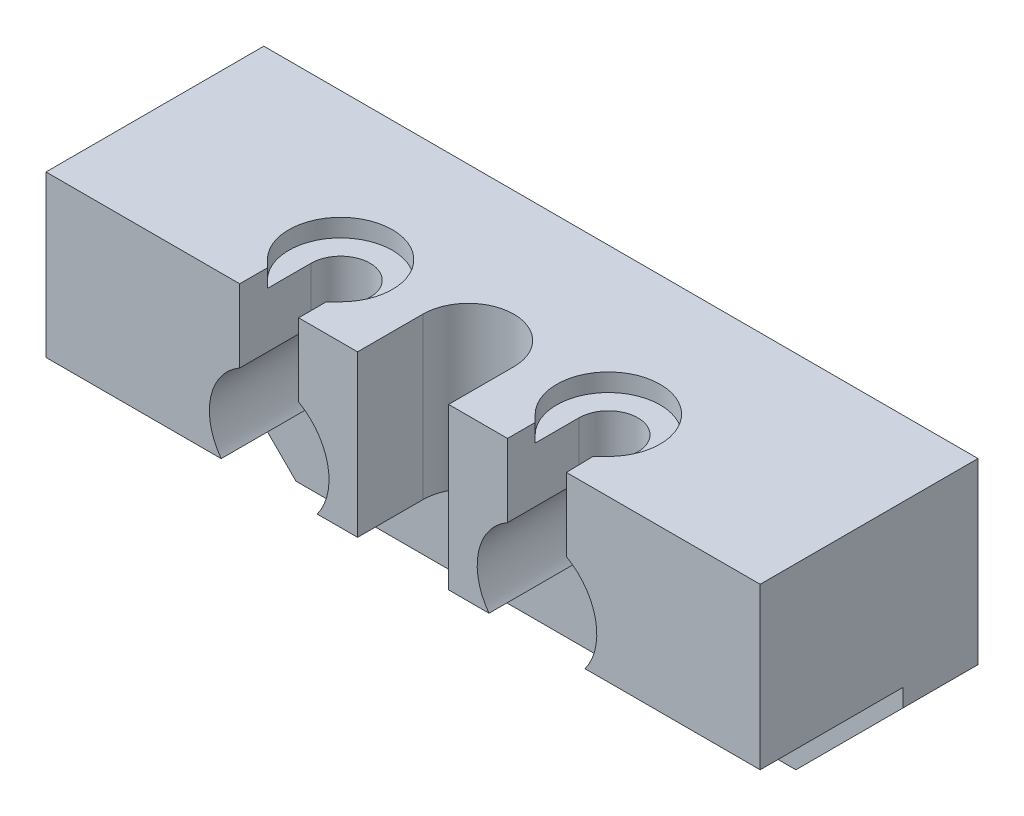
SolidWorks part; units mm, degrees
ref_plane "Front Plane" through (0, 0, 0) normal (0, 0, 1) x (1, 0, 0)
ref_plane "Top Plane" through (0, 0, 0) normal (0, 1, 0) x (1, 0, 0)
ref_plane "Right Plane" through (0, 0, 0) normal (1, 0, 0) x (0, 0, -1)
sketch "Sketch1" plane through (0, 0, 0) normal (0, 0, 1) x (1, 0, 0)
  line L1 (-20, 0) -> (20, 0)
  line L2 (-20, 0) -> (-20, 16)
  line L3 (-20, 16) -> (20, 16)
  line L4 (20, 0) -> (20, 16)
  dimension "D2" = 40
  dimension "D3" = 16
extrude "Boss-Extrude1" add sketch "Sketch1" along normal blind 12.5
sketch "Sketch2" plane through (0, 0, 12.5) normal (0, 0, 1) x (1, 0, 0)
  line L0 (0, 8) -> (0, 9) construction
  line L2 (-7.5, 9) -> (7.5, 9) construction
  line L3 (20, 16) -> (-20, 16) construction
  line L4 (-7.5, 5) -> (-7.5, 13) construction
  line L5 (-9.15, 5) -> (-9.15, 13) construction
  line L6 (-5.85, 5) -> (-5.85, 13) construction
  line L7 (7.5, 5) -> (7.5, 13) construction
  line L8 (5.85, 5) -> (5.85, 13) construction
  line L9 (9.15, 5) -> (9.15, 13) construction
  line L10 (-16, 8) -> (16, 8) construction
  arc A0 (-9.15, 5) -> (-5.85, 5) centre (-7.5, 5) ccw construction
  arc A1 (-5.85, 13) -> (-9.15, 13) centre (-7.5, 13) ccw construction
  arc A2 (5.85, 5) -> (9.15, 5) centre (7.5, 5) ccw construction
  arc A3 (9.15, 13) -> (5.85, 13) centre (7.5, 13) ccw construction
  circle A4 centre (-16, 8) radius 1.7784 construction
  circle A5 centre (16, 8) radius 1.7784 construction
  circle A6 centre (-7.5, 9) radius 1.65
  circle A7 centre (7.5, 9) radius 1.65
  point P8 (-7.5, 9)
  point P15 (7.5, 9)
  dimension "D1" = 1.65
  dimension "D2" = 8
  dimension "D3" = 7
  dimension "D4" = 15
  dimension "D5" = 1
  dimension "D6" = 32
extrude "Cut-Extrude1" cut sketch "Sketch2" against normal through all
sketch "Sketch5" plane through (0, 16, 0) normal (0, 1, 0) x (1, 0, 0)
  line L0 (0, 0) -> (0, -8.5) construction
  line L1 (-7.5, -8.5) -> (7.5, -8.5) construction
  line L2 (20, -12.5) -> (-20, -12.5) construction
  line L3 (-9.15, -8.5) -> (-9.15, -12.5)
  line L4 (-9.15, -12.5) -> (-5.85, -12.5)
  line L5 (-5.85, -12.5) -> (-5.85, -8.5)
  line L6 (5.85, -8.5) -> (5.85, -12.5)
  line L7 (5.85, -12.5) -> (9.15, -12.5)
  line L8 (9.15, -12.5) -> (9.073, -8.9981)
  arc A0 (-5.85, -8.5) -> (-9.15, -8.5) centre (-7.5, -8.5) ccw
  arc A1 (9.073, -8.9981) -> (5.85, -8.5) centre (7.5, -8.5) ccw
  dimension "D2" = 3.3
  dimension "D1" = 15
  dimension "D3" = 4
extrude "Cut-Extrude4" cut sketch "Sketch5" against normal through all
ref_axis "Axis1" through (7.5, 9, 8.5) along (0, 1, 0)
sketch "Sketch6" plane through (20, 0, 0) normal (1, 0, 0) x (0, 0, -1)
  line L0 (-12.5, 7) -> (-4.5, 7)
  line L3 (-4.5, 7) -> (-4.5, 0)
  line L4 (-12.5, 0) -> (0, 0) construction
  line L5 (-4.5, 0) -> (-12.5, 0)
  line L6 (-12.5, 0) -> (-12.5, 7)
  line L8 (-12.5, 16) -> (0, 16) construction
  line L9 (0, 0) -> (0, 16) construction
  dimension "D1" = 9
  dimension "D2" = 4.5
extrude "Cut-Extrude5" cut sketch "Sketch6" against normal through all
sketch "Sketch7" plane through (0, 16, 0) normal (0, 1, 0) x (1, 0, 0)
  line L1 (-9.5506, -10.5506) -> (-7.5, -12.6012)
  line L2 (-7.5, -12.6012) -> (-5.4494, -10.5506)
  line L3 (0, 0) -> (0, -12) construction
  line L4 (20, 0) -> (-20, 0) construction
  line L6 (7.5, -12.6012) -> (5.4494, -10.5506)
  line L7 (9.5506, -10.5506) -> (7.5, -12.6012)
  arc A0 (-5.4494, -10.5506) -> (-9.5506, -10.5506) centre (-7.5, -8.5) ccw
  arc A1 (5.4494, -10.5506) -> (9.5506, -10.5506) centre (7.5, -8.5) cw
  dimension "D1" = 5.8
extrude "Cut-Extrude6" cut sketch "Sketch7" against normal blind 1
chamfer "Chamfer4" [suppressed] distance 1.8 angle 45
sketch "Sketch8" plane through (0, 16, 0) normal (0, 1, 0) x (1, 0, 0)
  line L0 (-2.55, -8.8461) -> (-2.55, -12.5)
  line L1 (7.3988, -12.5) -> (-7.3988, -12.5) construction
  line L2 (-2.55, -12.5) -> (2.55, -12.5)
  line L3 (2.55, -12.5) -> (2.55, -8.8461)
  arc A0 (2.55, -9.0461) -> (-2.55, -9.0461) centre (0, -9.0461) ccw construction
  arc A1 (2.55, -8.8461) -> (-2.55, -8.8461) centre (0, -8.8461) ccw
  dimension "D1" = 2.55
  dimension "D2" = 0.2
extrude "Cut-Extrude7" cut sketch "Sketch8" against normal through all
sketch "Sketch9" plane through (0, 0, 12.5) normal (0, 0, 1) x (1, 0, 0)
  circle A0 centre (-7.5, 9) radius 3.35
  circle A1 centre (7.5, 9) radius 3.35
  dimension "D1" = 6.7
extrude "Cut-Extrude8" cut sketch "Sketch9" against normal up to surface (8 mm away) up to face at (0, 3.5, 4.5)
chamfer "Chamfer5" distance 1.8 angle 45 2 edges at (-7.5, 10.65, 4.5) (7.5, 10.65, 4.5)
chamfer "Chamfer6" distance 6 angle 45 2 edges at (20, 0, 2.25) (-20, 0, 2.25)
chamfer "Chamfer7" distance 0.3 angle 45 8 edges at (0, 16, 0) (-20, 11, 0) (-17, 3, 0) (0, 0, 0) (17, 3, 0) (20, 11, 0) (-5.85, 9, 0) (9.15, 9, 0)
sketch "Sketch10" plane through (0, 15, 0) normal (0, 1, 0) x (1, 0, 0)
  circle A0 centre (7.5, -8.5) radius 2.9
  circle A1 centre (-7.5, -8.5) radius 2.9
  arc A4 (-5.4494, -10.5506) -> (-9.5506, -10.5506) centre (-7.5, -8.5) ccw construction
  arc A5 (9.5506, -10.5506) -> (5.4494, -10.5506) centre (7.5, -8.5) ccw construction
  dimension "D1" = 5.8
extrude "Cut-Extrude9" [suppressed] cut sketch "Sketch10" against normal blind 0.5
equation "\"y-cross-rib-thickness\"=6"
equation "\"y-rib-thickness\"=6"
equation "\"bed-plate-thickness\"=6"
equation "\"x-plate-thickness\"=5"
equation "\"rod-diameter\"=12"
equation "\"t-nut-hole-diameter\"=3"
equation "\"y-plate-thickness\"=5"
equation "\"enclosure-thickness\"=0.6"
equation "\"M3-Clearance\"=3.3"
equation "\"M4-Clearance\"=4.3"
equation "\"M5-Clearance\"=5.3"
equation "\"M6-Clearance\"=6.3"
equation "\"M8-Clearance\"=8.3"
equation "\"623-Bearing-Dia\"=11.2"
